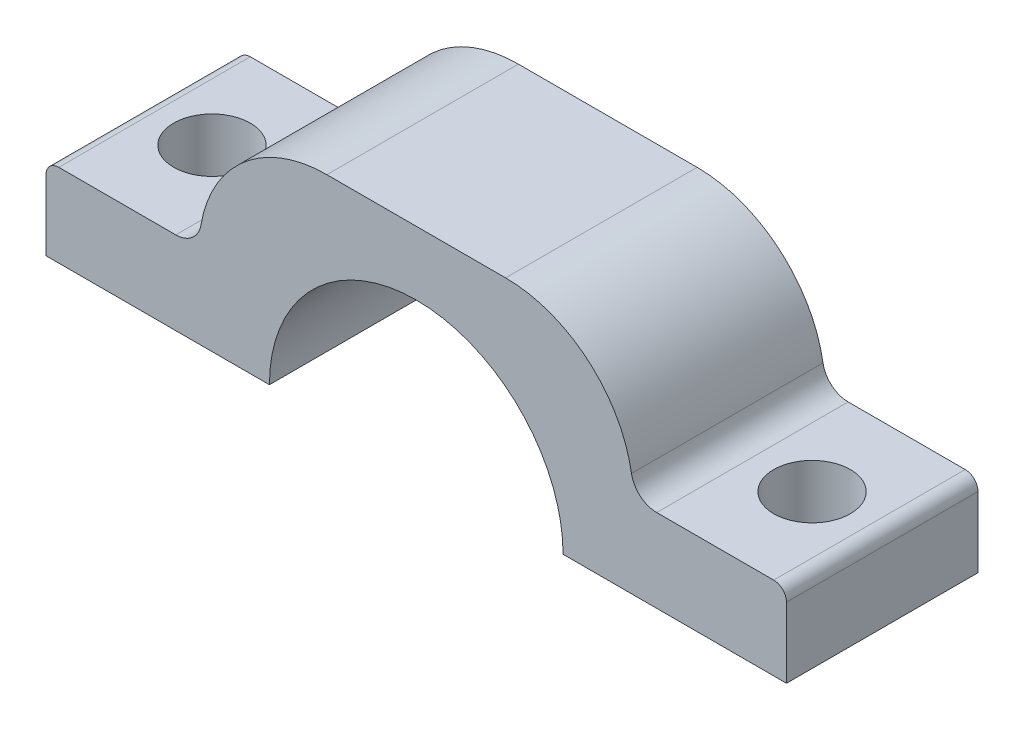
SolidWorks part; units mm, degrees
ref_plane "Płaszczyzna przednia" through (0, 0, 0) normal (0, 0, 1) x (1, 0, 0)
ref_plane "Płaszczyzna górna" through (0, 0, 0) normal (0, 1, 0) x (1, 0, 0)
ref_plane "Płaszczyzna prawa" through (0, 0, 0) normal (1, 0, 0) x (0, 0, -1)
sketch "Szkic1" plane through (0, 0, 0) normal (0, 0, 1) x (1, 0, 0)
  line L2 (-29, 0) -> (-29, 6.5)
  line L3 (-7, 16.5) -> (7, 16.5)
  line L4 (29, 0) -> (29, 6.5)
  line L7 (17, 6.5) -> (29, 6.5)
  line L9 (-17, 6.5) -> (-29, 6.5)
  line L10 (-11.5, 0) -> (-29, 0)
  line L11 (11.5, 0) -> (29, 0)
  arc A0 (11.5, 0) -> (-11.5, 0) centre (0, 0) ccw
  arc A3 (7, 16.5) -> (17, 6.5) centre (7, 6.5) cw
  arc A4 (-7, 16.5) -> (-17, 6.5) centre (-7, 6.5) ccw
  point P15 (17, 16.5)
  point P18 (-17, 16.5)
  point P21 (17, 6.5)
  point P24 (-17, 6.5)
  dimension "D1" = 23
  dimension "D4" = 6.5
  dimension "D8" = 10
  dimension "D9" = 16.5
  dimension "D7" = 14
  dimension "D2" = 17.5
  dimension "D3" = 17.5
  dimension "D5" = 12
  dimension "D6" = 6.5
extrude "Dodanie-wyciągnięcie1" add sketch "Szkic1" along normal blind 15
fillet "Zaokrąglenie1" radius 2 2 edges at (17, 6.5, 7.5) (-17, 6.5, 7.5)
hole_wizard "Otwory ustalające Ø6.0mm3" positions "Szkic6" profile "Szkic7" hole size "Ø6.0" standard "ISO" end condition through all
sketch "Szkic6" plane through (0, 6.5, 0) normal (0, 1, 0) x (1, 0, 0)
  line L0 (-29, -15) -> (-29, 0) construction
  line L1 (-18.8322, 0) -> (-29, 0) construction
  point P0 (-23.5, -7.5)
  dimension "D1" = 5.5
  dimension "D2" = 7.5
sketch "Szkic7" plane through (-23.5, 6.5, 7.5) normal (1, 0, 0) x (0, 0, 1)
  line L0 (0, 0) -> (0, 6.5)
  line L1 (0, 6.5) -> (3, 6.5)
  line L2 (3, 6.5) -> (3, 0)
  line L5 (3, 0) -> (0, 0)
  line L11 (0, -6.35) -> (0, 107.95) construction
  dimension "Średnica otworu na wylot" = 6
  dimension "Głębokość otworu na wylot" = 6.5
mirror "Lustro1" about plane through (0, 0, 0) normal (1, 0, 0) of "Otwory ustalające Ø6.0mm3"
fillet "Zaokrąglenie2" radius 1 2 edges at (29, 6.5, 7.5) (-29, 6.5, 7.5)
